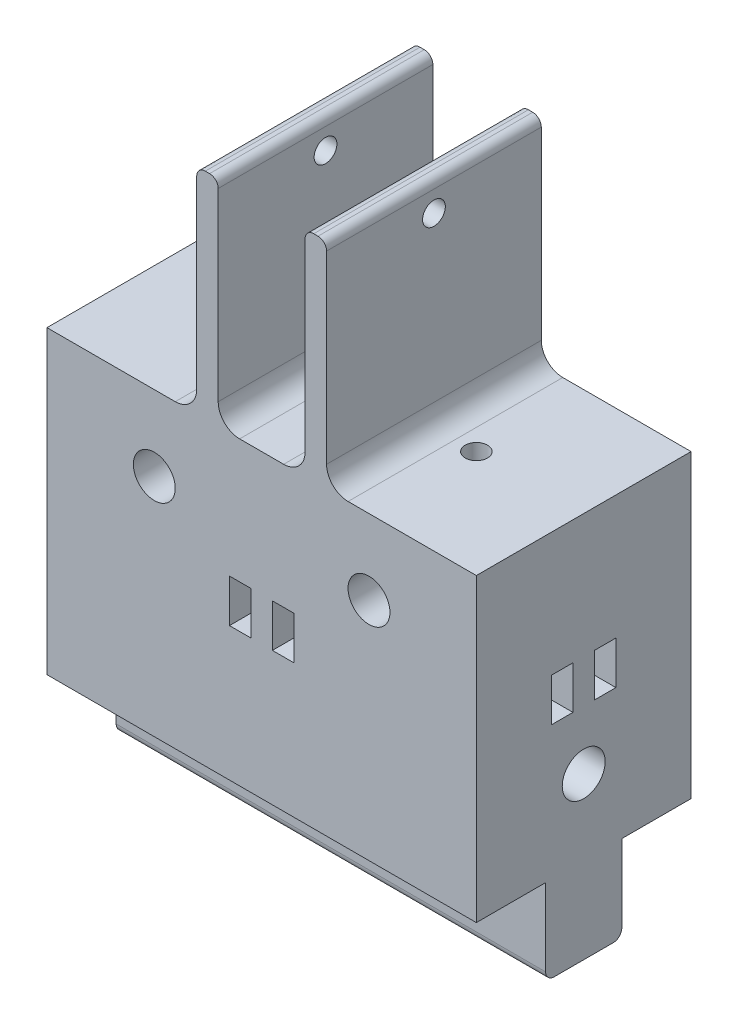
SolidWorks part; units mm, degrees
ref_plane "Front Plane" through (0, 0, 0) normal (0, 0, 1) x (1, 0, 0)
ref_plane "Top Plane" through (0, 0, 0) normal (0, 1, 0) x (1, 0, 0)
ref_plane "Right Plane" through (0, 0, 0) normal (1, 0, 0) x (0, 0, -1)
sketch "Sketch1" plane through (0, 0, 0) normal (0, 0, 1) x (1, 0, 0)
  line L1 (-50, -35) -> (50, -35)
  line L2 (-50, -35) -> (-50, 35)
  line L3 (-50, 35) -> (50, 35)
  line L4 (50, -35) -> (50, 35)
  line L5 (-50, -35) -> (50, 35) construction
  line L6 (-50, 35) -> (50, -35) construction
  point P0 (0, 0)
  dimension "D1" = 70
  dimension "D2" = 100
extrude "Boss-Extrude1" add sketch "Sketch1" along normal mid plane 50
sketch "Sketch2" plane through (0, 0, 25) normal (0, 0, 1) x (1, 0, 0)
  line L0 (0, 0) -> (50, 35) construction
  line L1 (0, 0) -> (-50, 35) construction
  circle A0 centre (25, 17.5) radius 4.875
  circle A1 centre (-25, 17.5) radius 4.875
  dimension "D1" = 9.75
extrude "Cut-Extrude1" cut sketch "Sketch2" against normal through all both and the other way through all
sketch "Sketch3" plane through (-50, 0, 0) normal (-1, 0, 0) x (0, 0, 1)
  line L0 (0, 0) -> (0, -35) construction
  line L1 (25, -35) -> (-25, -35) construction
  circle A0 centre (0, -17.5) radius 5
  dimension "D1" = 10
extrude "Cut-Extrude2" cut sketch "Sketch3" against normal through all both
sketch "Sketch4" plane through (0, 35, 0) normal (0, 1, 0) x (1, 0, 0)
  line L0 (-50, 0) -> (0, 0) construction
  line L1 (-50, -25) -> (-50, 25) construction
  line L3 (0, 0) -> (50, 0) construction
  line L4 (50, -25) -> (50, 25) construction
  circle A0 centre (-25, 0) radius 2.6
  circle A1 centre (25, 0) radius 2.6
  point P5 (-25, 0)
  dimension "D1" = 5.2
extrude "Cut-Extrude4" cut sketch "Sketch4" against normal blind 20
sketch "Sketch5" plane through (0, -35, 0) normal (0, -1, 0) x (1, 0, 0)
  line L0 (50, 25) -> (50, -25) construction
  line L1 (-50, -8.875) -> (50, -8.875)
  line L2 (-50, -8.875) -> (-50, 8.875)
  line L3 (-50, 8.875) -> (50, 8.875)
  line L4 (50, -8.875) -> (50, 8.875)
  line L5 (-50, -8.875) -> (50, 8.875) construction
  line L6 (-50, 8.875) -> (50, -8.875) construction
  point P0 (0, 0)
  dimension "D1" = 17.75
extrude "Boss-Extrude2" add sketch "Sketch5" along normal blind 20
fillet "Fillet1" radius 2 2 edges at (0, -55, -8.875) (0, -55, 8.875)
sketch "Sketch6" plane through (0, 35, 0) normal (0, 1, 0) x (1, 0, 0)
  line L0 (50, 25) -> (-50, 25) construction
  line L1 (-15.125, 25) -> (-10.125, 25)
  line L2 (-15.125, 25) -> (-15.125, -25)
  line L3 (-15.125, -25) -> (-10.125, -25)
  line L4 (-10.125, 25) -> (-10.125, -25)
  line L5 (50, -25) -> (-50, -25) construction
  line L6 (-10.125, 0) -> (10.125, 0) construction
  line L7 (15.125, 25) -> (10.125, 25)
  line L8 (15.125, 25) -> (15.125, -25)
  line L9 (15.125, -25) -> (10.125, -25)
  line L10 (10.125, 25) -> (10.125, -25)
  point P16 (0, 0)
  dimension "D1" = 20.25
  dimension "D2" = 5
extrude "Boss-Extrude3" add sketch "Sketch6" along normal blind 50
sketch "Sketch7" plane through (15.125, 0, 0) normal (1, 0, 0) x (0, 0, -1)
  line L0 (0, 85) -> (0, 78.15) construction
  line L1 (-25, 85) -> (25, 85) construction
  circle A0 centre (0, 78.15) radius 2.65
  dimension "D2" = 5.3
  dimension "D1" = 6.85
extrude "Cut-Extrude5" cut sketch "Sketch7" against normal through all both
fillet "Fillet2" radius 5 4 edges at (-15.125, 35, 0) (-10.125, 35, 0) (10.125, 35, 0) (15.125, 35, 0)
fillet "Fillet3" radius 2 4 edges at (15.125, 85, 0) (10.125, 85, 0) (-10.125, 85, 0) (-15.125, 85, 0)
sketch "Sketch8" plane through (-50, 0, 0) normal (-1, 0, 0) x (0, 0, 1)
  line L0 (0, 35) -> (0, 6.15) construction
  line L1 (-2.5, -3.85) -> (-2.5, 6.15)
  line L2 (-7.5, 6.15) -> (7.5, 6.15)
  line L3 (-7.5, 6.15) -> (-7.5, -3.85)
  line L4 (-7.5, -3.85) -> (7.5, -3.85)
  line L5 (7.5, 6.15) -> (7.5, -3.85)
  line L6 (2.5, -3.85) -> (2.5, 6.15)
  line L7 (25, 35) -> (-25, 35) construction
  point P6 (0, 6.15)
  point P14 (0, 35)
  dimension "D1" = 28.85
  dimension "D2" = 15
  dimension "D3" = 10
  dimension "D4" = 5
  dimension "D5" = 5
extrude "Cut-Extrude6" cut sketch "Sketch8" against normal through all both contours L6 L4 L5 L2 | L3 L4 L1 L2 region at (-50, 1.15, -5) region at (-50, 1.15, 5)
sketch "Sketch9" plane through (0, 0, 25) normal (0, 0, 1) x (1, 0, 0)
  line L0 (0, -35) -> (0, 6.15)
  line L1 (-7.5, 6.15) -> (7.5, 6.15)
  line L2 (-7.5, 6.15) -> (-7.5, -3.85)
  line L3 (-7.5, -3.85) -> (7.5, -3.85)
  line L4 (7.5, 6.15) -> (7.5, -3.85)
  line L5 (-2.5, 6.15) -> (2.5, 6.15)
  line L6 (-2.5, 6.15) -> (-2.5, -3.85)
  line L7 (-2.5, -3.85) -> (2.5, -3.85)
  line L8 (2.5, 6.15) -> (2.5, -3.85)
  line L9 (-50, -35) -> (50, -35) construction
  line L10 (-20.125, 35) -> (-50, 35) construction
  point P6 (0, 6.15)
  point P14 (0, -35)
  dimension "D1" = 15
  dimension "D2" = 10
  dimension "D3" = 5
  dimension "D4" = 5
  dimension "D5" = 28.85
extrude "Cut-Extrude7" cut sketch "Sketch9" against normal through all both contours L1 L8 L3 L4 | L6 L1 L2 L3 region at (-5, 1.15, 25) region at (5, 1.15, 25)
fillet "Fillet4" radius 10 4 edges at (7.5, 1.15, 7.5) (7.5, 1.15, -7.5) (-7.5, 1.15, -7.5) (-7.5, 1.15, 7.5)
